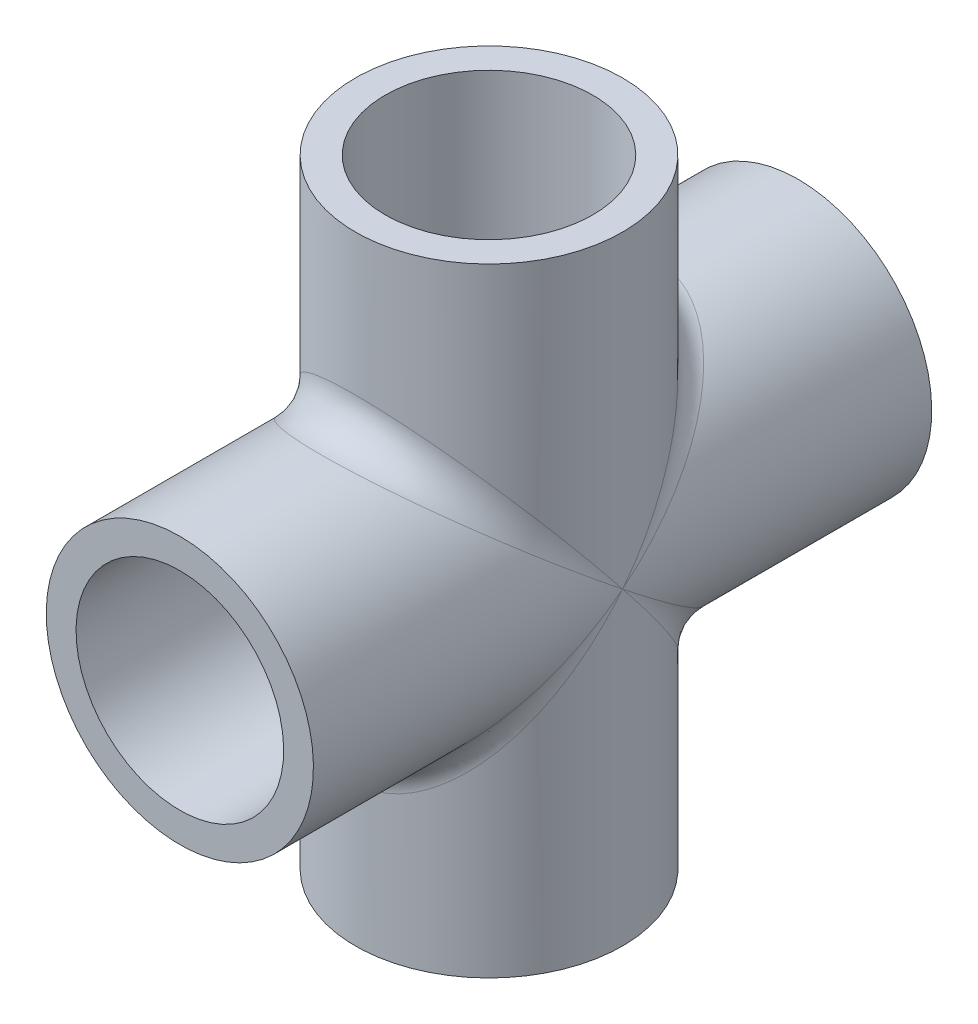
SolidWorks part; units mm, degrees
ref_plane "Front Plane" through (0, 0, 0) normal (0, 0, 1) x (1, 0, 0)
ref_plane "Top Plane" through (0, 0, 0) normal (0, 1, 0) x (1, 0, 0)
ref_plane "Right Plane" through (0, 0, 0) normal (1, 0, 0) x (0, 0, -1)
sketch "Sketch1" plane through (0, 0, 0) normal (1, 0, 0) x (0, 0, -1)
  line L0 (0, 0) -> (-32.1469, 0) construction
  line L1 (0, 0) -> (32.1469, 0) construction
  line L2 (0, 0) -> (0, 32.1469) construction
  line L3 (-13.4937, -7.8994) -> (-13.4938, 7.8994) construction
  line L4 (-7.8994, 13.4937) -> (7.8994, 13.4937) construction
  line L5 (13.4937, -7.8994) -> (13.4937, 7.8994) construction
  line L6 (-32.1469, -13.8906) -> (-32.1469, 13.8906) construction
  line L7 (32.1469, -13.8906) -> (32.1469, 13.8906) construction
  line L8 (13.8906, 32.1469) -> (-13.8906, 32.1469) construction
  line L9 (-13.4938, 7.8994) -> (-32.1469, 7.8994) construction
  line L10 (-7.8994, 13.4937) -> (-7.8994, 32.1469) construction
  line L11 (13.4937, 7.8994) -> (32.1469, 7.8994) construction
  line L12 (-22.8203, -10.795) -> (-22.8203, 10.795) construction
  line L13 (-10.795, 22.8203) -> (10.795, 22.8203) construction
  line L14 (22.8203, -10.795) -> (22.8203, 10.795) construction
  line L15 (0, 0) -> (0, -32.1469) construction
  line L16 (-13.8906, -32.1469) -> (13.8906, -32.1469) construction
  line L17 (-7.8994, -13.4938) -> (7.8994, -13.4937) construction
  line L18 (-10.795, -22.8203) -> (10.795, -22.8203) construction
  line L19 (7.8994, -13.4937) -> (7.8994, -32.1469) construction
  point P4 (0, 0)
  point P10 (-13.4937, 0)
  point P13 (0, 13.4937)
  point P16 (13.4937, 0)
  point P19 (-32.1469, 0)
  point P22 (32.1469, 0)
  point P25 (0, 32.1469)
  point P27 (-22.8203, 7.8994)
  point P31 (-22.8203, 0)
  point P34 (0, 22.8203)
  point P37 (22.8203, 0)
  point P38 (-7.8994, 22.8203)
  point P39 (22.8203, 7.8994)
  point P42 (0, -32.1469)
  point P46 (0, -13.4937)
  point P49 (0, -22.8203)
  point P50 (7.8994, -22.8203)
  dimension "Horz Leg Length" = 32.1469
  dimension "Vert Leg Length" = 32.1469
  dimension "Horz Length" = 64.2938
  dimension "Horz Center to Socket" = 13.4937
  dimension "D1" = 13.4937
  dimension "Vert Center to Socket" = 13.4937
  dimension "Pipe ID" = 15.7988
  dimension "Tee OD" = 27.7812
  dimension "For Pipe OD" = 21.59
  dimension "D2" = 13.4937
  dimension "Vert Length" = 64.2938
sketch "Sketch2" plane through (0, 0, 0) normal (1, 0, 0) x (0, 0, -1)
  line L0 (-32.1469, 13.8906) -> (32.1469, 13.8906)
  line L1 (32.1469, 13.8906) -> (32.1469, 0)
  line L2 (32.1469, -13.8906) -> (32.1469, 13.8906) construction
  line L8 (-32.1469, -13.8906) -> (-32.1469, 13.8906) construction
  line L9 (-32.1469, 0) -> (-32.1469, 13.8906)
  line L10 (-32.1469, 0) -> (32.1469, 0)
revolve "Revolve1" add sketch "Sketch2" angle 360 about L0
sketch "Sketch3" plane through (0, 0, 0) normal (1, 0, 0) x (0, 0, -1)
  line L0 (0, 32.1469) -> (13.8906, 32.1469)
  line L1 (13.8906, 32.1469) -> (13.8906, -32.1469)
  line L3 (13.8906, -32.1469) -> (0, -32.1469)
  line L4 (0, -32.1469) -> (0, 32.1469)
revolve "Revolve2" add sketch "Sketch3" angle 360 about L2
sketch "Sketch4" plane through (0, 0, 0) normal (1, 0, 0) x (0, 0, -1)
  line L0 (-32.1469, 10.795) -> (-13.4938, 10.795)
  line L1 (-32.1469, -13.8906) -> (-32.1469, 13.8906) construction
  line L2 (-13.4938, 10.795) -> (-13.4938, 7.8994)
  line L3 (-13.4938, 7.8994) -> (13.4937, 7.8994)
  line L4 (13.4937, 7.8994) -> (13.4937, 10.795)
  line L5 (13.4937, 10.795) -> (32.1469, 10.795)
  line L6 (32.1469, -13.8906) -> (32.1469, 13.8906) construction
  line L7 (32.1469, 10.795) -> (32.1469, 0)
  line L8 (32.1469, 0) -> (-32.1469, 0)
  line L9 (-32.1469, 0) -> (-32.1469, 10.795)
revolve "Cut-Revolve1" cut sketch "Sketch4" angle 360 about L8
sketch "Sketch5" plane through (0, 0, 0) normal (1, 0, 0) x (0, 0, -1)
  line L0 (0, 32.1469) -> (0, -32.1469)
  line L1 (13.8906, 32.1469) -> (-13.8906, 32.1469) construction
  line L3 (0, -32.1469) -> (-10.795, -32.1469)
  line L5 (-7.8994, -13.4938) -> (-7.8994, 13.4937)
  line L6 (-7.8994, 13.4937) -> (-10.795, 13.4937)
  line L7 (-10.795, 13.4937) -> (-10.795, 32.1469)
  line L8 (-10.795, 32.1469) -> (0, 32.1469)
  line L9 (-13.8906, -32.1469) -> (13.8906, -32.1469) construction
  line L10 (-10.795, -32.1469) -> (-10.795, -13.4938)
  line L11 (-10.795, -13.4938) -> (-7.8994, -13.4938)
revolve "Cut-Revolve2" cut sketch "Sketch5" angle 360 about L0
fillet "Fillet1" radius 3.5847 4 edges at (0, -13.8906, 13.8906) (0, 13.8906, -13.8906) (0, -13.8906, -13.8906) (0, 13.8906, 13.8906)
sketch "Sketch6" plane through (0, 0, 0) normal (1, 0, 0) x (0, 0, -1)
  line L0 (-32.1469, 10.795) -> (-13.4938, 10.795)
  line L1 (-32.1469, -13.8906) -> (-32.1469, 13.8906) construction
  line L2 (-13.4938, 10.795) -> (-13.4938, 7.8994)
  line L3 (-13.4938, 7.8994) -> (-7.8994, 7.8994)
  line L4 (-7.8994, 7.8994) -> (-7.8994, 13.4937)
  line L5 (-7.8994, 13.4937) -> (-10.795, 13.4937)
  line L6 (-10.795, 13.4937) -> (-10.795, 32.1469)
  line L7 (13.8906, 32.1469) -> (-13.8906, 32.1469) construction
  line L8 (-13.4937, -7.8994) -> (-7.8994, -7.8994)
  line L9 (13.4937, -7.8994) -> (13.4937, -10.795)
  line L10 (13.4937, -10.795) -> (32.1469, -10.795)
  line L11 (32.1469, -13.8906) -> (32.1469, 13.8906) construction
  line L12 (-13.4937, -7.8994) -> (-13.4937, -10.795)
  line L13 (-13.4937, -10.795) -> (-32.1469, -10.795)
  line L14 (32.1469, 10.795) -> (13.4937, 10.795)
  line L15 (13.4937, 10.795) -> (13.4937, 7.8994)
  line L16 (13.4937, 7.8994) -> (7.8994, 7.8994)
  line L17 (7.8994, 7.8994) -> (7.8994, 13.4937)
  line L18 (7.8994, 13.4937) -> (10.795, 13.4938)
  line L19 (10.795, 13.4938) -> (10.795, 32.1469)
  line L20 (-7.8994, -13.4938) -> (-7.8994, -7.8994)
  line L21 (7.8994, -13.4937) -> (7.8994, -7.8994)
  line L22 (10.795, -32.1469) -> (10.795, -13.4937)
  line L23 (-13.8906, -32.1469) -> (13.8906, -32.1469) construction
  line L24 (10.795, -13.4937) -> (7.8994, -13.4937)
  line L25 (-10.795, -32.1469) -> (-10.795, -13.4938)
  line L26 (-10.795, -13.4938) -> (-7.8994, -13.4938)
  line L27 (7.8994, -7.8994) -> (13.4937, -7.8994)
sketch "Sketch7" plane through (0, 0, 32.1469) normal (0, 0, 1) x (1, 0, 0)
  circle A0 centre (0, 0) radius 10.795 construction
  circle A1 centre (0, 0) radius 10.795
  point P3 (0, -10.795)
  point P4 (10.795, 0)
  point P5 (-10.795, 0)
  point P6 (0, 10.795)
equation "\"D1@Fillet1\"=\"Tee OD@Sketch1\"*0.1290322581"
equation "\"D2@Sketch1\"=\"Vert Center to Socket@Sketch1\""
equation "\"Horz Leg Length@Sketch1\" = \"Horz Length@Sketch1\" / 2"
equation "\"Vert Leg Length@Sketch1\"=\"Vert Length@Sketch1\"/2"
equation "\"D1@Sketch1\"=\"Horz Center to Socket@Sketch1\""
